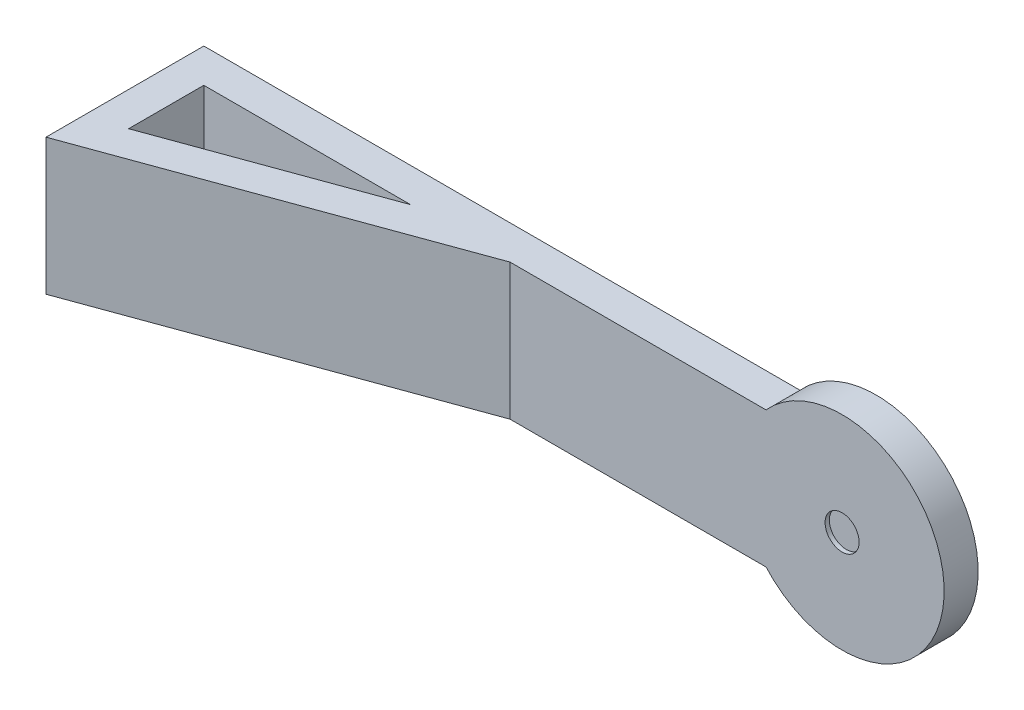
SolidWorks part; units mm, degrees
ref_plane "Front Plane" through (0, 0, 0) normal (0, 0, 1) x (1, 0, 0)
ref_plane "Top Plane" through (0, 0, 0) normal (0, 1, 0) x (1, 0, 0)
ref_plane "Right Plane" through (0, 0, 0) normal (1, 0, 0) x (0, 0, -1)
sketch "Sketch2" plane through (0, 0, 0) normal (0, 0, 1) x (1, 0, 0)
  line L0 (0, 0) -> (0, 29.4621)
  line L1 (0, 29.4621) -> (63.5, 6.35)
  line L2 (63.5, 6.35) -> (139.7, 6.35)
  line L3 (139.7, 6.35) -> (139.7, 0)
  line L4 (139.7, 0) -> (0, 0)
  line L5 (44.9338, 6.35) -> (6.35, 6.35)
  line L6 (6.35, 6.35) -> (6.35, 20.3934)
  line L7 (6.35, 20.3934) -> (44.9338, 6.35)
  dimension "D1" = 6.35
  dimension "D2" = 160
  dimension "D3" = 6.35
  dimension "D4" = 6.35
  dimension "D5" = 63.5
  dimension "D6" = 139.7
extrude "Boss-Extrude1" add sketch "Sketch2" along normal blind 25.4
sketch "Sketch3" plane through (0, 6.35, 0) normal (0, 1, 0) x (1, 0, 0)
  line L0 (139.7, -12.7) -> (63.5, -12.7) construction
  line L1 (139.7, -25.4) -> (139.7, 0) construction
  line L2 (63.5, -25.4) -> (63.5, 0) construction
  circle A0 centre (125.501, -12.7) radius 19.05
  circle A1 centre (125.501, -12.7) radius 3.175
  dimension "D1" = 38.1
  dimension "D2" = 6.35
extrude "Boss-Extrude2" add sketch "Sketch3" against normal up to surface (6.35 mm away) up to face at (69.85, 0, 12.7)
extrude "Cut-Extrude1" cut sketch "Sketch3<2>" against normal blind 25.4 contours L0 A1 | A1 L0 region at (125.501, 6.35, 14.0475) region at (125.501, 6.35, 11.3525)
sketch "Sketch3<2>" plane through (0, 6.35, 0) normal (0, 1, 0) x (1, 0, 0) same geometry as "Sketch3"
extrude "Boss-Extrude3" add sketch "Sketch3<3>" against normal offset from surface (4.7625 mm away) 0.7937 from offset 0.7937 contours L0 A1 | A1 L0 region at (125.501, 6.35, 14.0475) region at (125.501, 6.35, 11.3525) up to face at (122.326, 0, 12.7) offset against normal yes
sketch "Sketch3<3>" plane through (0, 6.35, 0) normal (0, 1, 0) x (1, 0, 0) same geometry as "Sketch3"
move or copy body "Body-Move/Copy1" bodies to move or copy 105 copy no rotation origin (0, 0, 0) rotation axis (1, 0, 0) rotation angle 90
